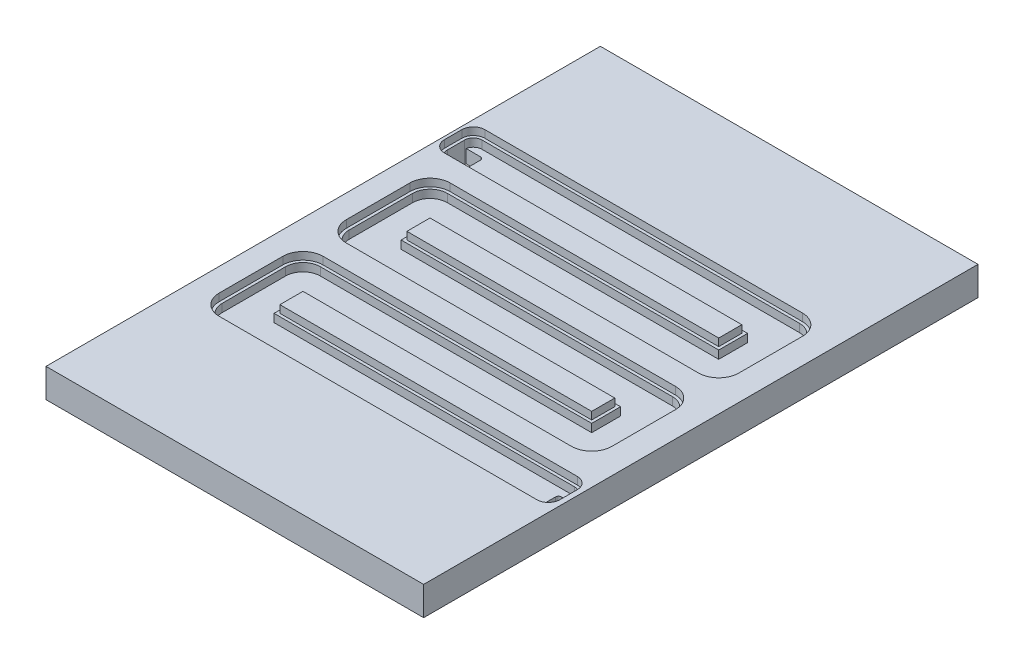
SolidWorks part; units mm, degrees
ref_plane "前视基准面" through (0, 0, 0) normal (0, 0, 1) x (1, 0, 0)
ref_plane "上视基准面" through (0, 0, 0) normal (0, 1, 0) x (1, 0, 0)
ref_plane "右视基准面" through (0, 0, 0) normal (1, 0, 0) x (0, 0, -1)
sketch "草图1" plane through (0, 0, 0) normal (0, 1, 0) x (1, 0, 0)
  line L0 (5, -275) -> (5, -245)
  line L1 (0, 0) -> (654, 0)
  line L2 (0, 0) -> (0, -960)
  line L3 (0, -960) -> (654, -960)
  line L4 (654, 0) -> (654, -960)
  line L5 (25, -225) -> (575, -225)
  line L6 (610, -260) -> (610, -370)
  line L7 (575, -405) -> (110, -405)
  line L8 (110, -405) -> (110, -445)
  line L9 (110, -445) -> (575, -445)
  line L10 (610, -480) -> (610, -590)
  line L11 (575, -625) -> (110, -625)
  line L12 (110, -625) -> (110, -665)
  line L13 (110, -665) -> (625, -665)
  line L14 (645, -685) -> (645, -715)
  line L15 (625, -735) -> (75, -735)
  line L16 (40, -700) -> (40, -590)
  line L17 (75, -555) -> (540, -555)
  line L18 (540, -555) -> (540, -515)
  line L19 (540, -515) -> (75, -515)
  line L20 (40, -480) -> (40, -370)
  line L21 (75, -335) -> (540, -335)
  line L22 (540, -335) -> (540, -295)
  line L23 (540, -295) -> (25, -295)
  line L24 (25, -230) -> (575, -230)
  line L25 (605, -260) -> (605, -370)
  line L26 (575, -400) -> (105, -400)
  line L27 (105, -400) -> (105, -450)
  line L28 (105, -450) -> (575, -450)
  line L29 (605, -480) -> (605, -590)
  line L30 (575, -620) -> (105, -620)
  line L31 (105, -620) -> (105, -670)
  line L32 (105, -670) -> (625, -670)
  line L33 (640, -685) -> (640, -715)
  line L34 (625, -730) -> (75, -730)
  line L35 (45, -700) -> (45, -590)
  line L36 (75, -560) -> (545, -560)
  line L37 (545, -560) -> (545, -510)
  line L38 (545, -510) -> (75, -510)
  line L39 (45, -480) -> (45, -370)
  line L40 (75, -340) -> (545, -340)
  line L41 (545, -340) -> (545, -290)
  line L42 (545, -290) -> (25, -290)
  line L43 (10, -275) -> (10, -245)
  line L44 (640, -730) -> (45, -730) construction
  line L45 (45, -730) -> (45, -560) construction
  line L46 (45, -560) -> (545, -560) construction
  line L47 (605, -450) -> (605, -620) construction
  line L48 (605, -620) -> (105, -620) construction
  line L49 (105, -450) -> (605, -450) construction
  line L50 (545, -510) -> (45, -510) construction
  line L51 (45, -510) -> (45, -340) construction
  line L52 (45, -340) -> (545, -340) construction
  line L53 (605, -230) -> (605, -400) construction
  line L54 (605, -400) -> (105, -400) construction
  line L55 (10, -230) -> (605, -230) construction
  line L56 (645, -665) -> (645, -735) construction
  line L57 (645, -735) -> (40, -735) construction
  line L58 (110, -665) -> (645, -665) construction
  line L59 (5, -295) -> (5, -225) construction
  line L60 (540, -295) -> (5, -295) construction
  line L61 (5, -225) -> (610, -225) construction
  line L62 (545, -290) -> (10, -290) construction
  line L63 (10, -290) -> (10, -230) construction
  line L64 (640, -670) -> (640, -730) construction
  line L65 (105, -670) -> (640, -670) construction
  line L66 (40, -735) -> (40, -555) construction
  line L67 (40, -555) -> (540, -555) construction
  line L68 (610, -445) -> (610, -625) construction
  line L69 (610, -625) -> (110, -625) construction
  line L70 (110, -445) -> (610, -445) construction
  line L71 (540, -515) -> (40, -515) construction
  line L72 (40, -515) -> (40, -335) construction
  line L73 (40, -335) -> (540, -335) construction
  line L74 (610, -225) -> (610, -405) construction
  line L75 (610, -405) -> (110, -405) construction
  line L77 (35, -277.5) -> (10, -277.5)
  line L78 (40, -272.5) -> (40, -247.5)
  line L79 (35, -242.5) -> (10, -242.5)
  line L80 (5, -272.5) -> (5, -247.5)
  line L81 (40, -277.5) -> (5, -242.5) construction
  line L82 (40, -242.5) -> (5, -277.5) construction
  line L83 (640, -717.5) -> (615, -717.5)
  line L84 (645, -712.5) -> (645, -687.5)
  line L85 (640, -682.5) -> (615, -682.5)
  line L86 (610, -712.5) -> (610, -687.5)
  line L87 (645, -717.5) -> (610, -682.5) construction
  line L88 (645, -682.5) -> (610, -717.5) construction
  arc A0 (75, -730) -> (45, -700) centre (75, -700) cw
  arc A1 (45, -590) -> (75, -560) centre (75, -590) cw
  arc A2 (605, -590) -> (575, -620) centre (575, -590) cw
  arc A3 (575, -450) -> (605, -480) centre (575, -480) cw
  arc A4 (75, -510) -> (45, -480) centre (75, -480) cw
  arc A5 (45, -370) -> (75, -340) centre (75, -370) cw
  arc A6 (605, -370) -> (575, -400) centre (575, -370) cw
  arc A7 (575, -230) -> (605, -260) centre (575, -260) cw
  arc A8 (645, -715) -> (625, -735) centre (625, -715) cw
  arc A9 (625, -665) -> (645, -685) centre (625, -685) cw
  arc A10 (5, -275) -> (25, -295) centre (25, -275) ccw
  arc A11 (5, -245) -> (25, -225) centre (25, -245) cw
  arc A12 (25, -290) -> (10, -275) centre (25, -275) cw
  arc A13 (25, -230) -> (10, -245) centre (25, -245) ccw
  arc A14 (640, -715) -> (625, -730) centre (625, -715) cw
  arc A15 (625, -670) -> (640, -685) centre (625, -685) cw
  arc A16 (75, -735) -> (40, -700) centre (75, -700) cw
  arc A17 (40, -590) -> (75, -555) centre (75, -590) cw
  arc A18 (610, -590) -> (575, -625) centre (575, -590) cw
  arc A19 (575, -445) -> (610, -480) centre (575, -480) cw
  arc A20 (75, -515) -> (40, -480) centre (75, -480) cw
  arc A21 (40, -370) -> (75, -335) centre (75, -370) cw
  arc A22 (610, -370) -> (575, -405) centre (575, -370) cw
  arc A23 (575, -225) -> (610, -260) centre (575, -260) cw
  arc A24 (35, -277.5) -> (40, -272.5) centre (35, -272.5) ccw
  arc A25 (10, -277.5) -> (5, -272.5) centre (10, -272.5) cw
  arc A26 (10, -242.5) -> (5, -247.5) centre (10, -247.5) ccw
  arc A27 (40, -247.5) -> (35, -242.5) centre (35, -247.5) ccw
  arc A28 (640, -717.5) -> (645, -712.5) centre (640, -712.5) ccw
  arc A29 (615, -717.5) -> (610, -712.5) centre (615, -712.5) cw
  arc A30 (645, -687.5) -> (640, -682.5) centre (640, -687.5) ccw
  arc A31 (615, -682.5) -> (610, -687.5) centre (615, -687.5) ccw
  point P45 (645, -700)
  point P46 (10, -260)
  point P119 (22.5, -260)
  point P124 (627.5, -700)
  point P129 (0, 0)
  point P130 (0, 0)
  point P131 (640, -700)
  dimension "D22" = 30
  dimension "D23" = 20
  dimension "D24" = 15
  dimension "D25" = 35
  dimension "D32" = 5
  dimension "D1" = 654
  dimension "D2" = 960
  dimension "D3" = 5
  dimension "D5" = 60
  dimension "D6" = 60
  dimension "D7" = 60
  dimension "D8" = 60
  dimension "D9" = 60
  dimension "D10" = 60
  dimension "D11" = 60
  dimension "D12" = 60
  dimension "D13" = 60
  dimension "D14" = 535
  dimension "D15" = 260
  dimension "D16" = 440
  dimension "D17" = 430
  dimension "D18" = 170
  dimension "D19" = 170
  dimension "D20" = 170
  dimension "D21" = 9
  dimension "D26" = 35
  dimension "D27" = 35
  dimension "D28" = 26.5
  dimension "D29" = 605
  dimension "D30" = 35
  dimension "D31" = 35
  dimension "D4" = 5
extrude "凸台-拉伸1" add sketch "草图1" against normal blind 50 contours L3 L4 L1 L2
extrude "切除-拉伸1" cut sketch "草图1<4>" against normal blind 13 contours L15 A16 L16 A17 L17 L18 L19 A20 L20 A21 L21 L22 L23 A10 L0 A11 L5 A23 L6 A22 L7 L8 L9 A19 L10 A18 L11 L12 L13 A9 L14 A8
sketch "草图1<4>" plane through (0, 0, 0) normal (0, 1, 0) x (1, 0, 0) same geometry as "草图1"
extrude "切除-拉伸2" cut sketch "草图1<5>" against normal blind 27 contours L34 A0 L35 A1 L36 L37 L38 A4 L39 A5 L40 L41 L42 A12 L43 A13 L24 A7 L25 A6 L26 L27 L28 A3 L29 A2 L30 L31 L32 A15 L33 A14
sketch "草图1<5>" plane through (0, 0, 0) normal (0, 1, 0) x (1, 0, 0) same geometry as "草图1"
extrude "切除-拉伸3" cut sketch "草图1<6>" against normal blind 50 contours L78 A27 L79 A13 L43 A12 L77 A24 | L86 A31 L85 A30 L84 A28 L83 A29 region at (24.8616, 0, 260)
sketch "草图1<6>" plane through (0, 0, 0) normal (0, 1, 0) x (1, 0, 0) same geometry as "草图1"
